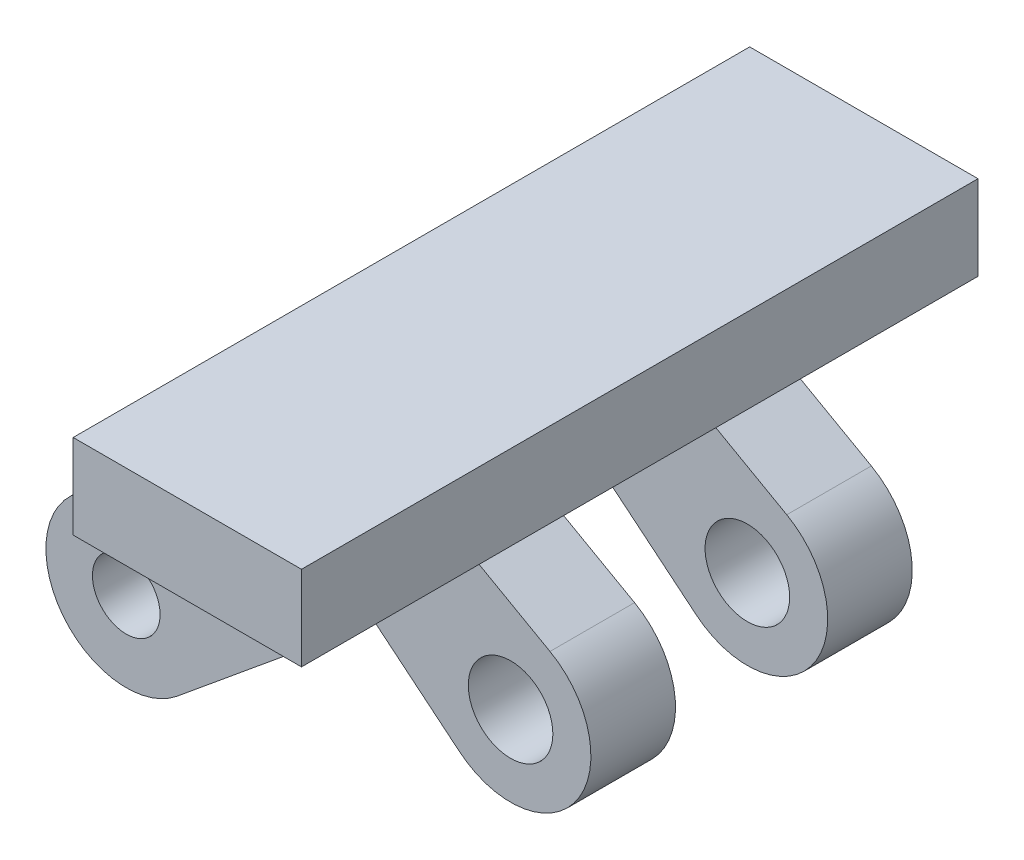
SolidWorks part; units mm, degrees
ref_plane "前视基准面" through (0, 0, 0) normal (0, 0, 1) x (1, 0, 0)
ref_plane "上视基准面" through (0, 0, 0) normal (0, 1, 0) x (1, 0, 0)
ref_plane "右视基准面" through (0, 0, 0) normal (1, 0, 0) x (0, 0, -1)
sketch "草图1" plane through (0, 0, 0) normal (0, 0, 1) x (1, 0, 0)
  line L1 (0, 0) -> (5.4, 0)
  line L2 (0, 0) -> (0, -2)
  line L3 (0, -2) -> (5.4, -2)
  line L4 (5.4, 0) -> (5.4, -2)
  dimension "D1" = 2
  dimension "D2" = 5.4
extrude "凸台-拉伸1" add sketch "草图1" along normal blind 8 and the other way blind 8
ref_plane "基准面2" through (0, 0, 6) normal (0, 0, 1) x (1, 0, 0)
sketch "草图3" plane through (0, 0, 6) normal (0, 0, 1) x (1, 0, 0)
  line L0 (0, -2) -> (-1.6772, -2.9444)
  line L1 (5.4, -2) -> (0.463, -6.0666)
  line L2 (0, -2) -> (5.4, -2) construction
  line L3 (0, -2) -> (5.4, -2)
  circle A0 centre (-0.745, -4.6) radius 1.9
  circle A1 centre (-0.745, -4.6) radius 0.8
  point P14 (2.7, -2)
  dimension "D1" = 1.6
  dimension "D2" = 3.8
  dimension "D3" = 2.6
  dimension "D4" = 3.445
extrude "凸台-拉伸2" add sketch "草图3" against normal blind 2 contours A0 A1 | A0 L1 L3 L0 region at (2.0907, -3.0871, 6) region at (0.1867, -3.0061, 6)
ref_plane "基准面1" through (0, 0, 3.8) normal (0, 0, 1) x (1, 0, 0)
sketch "草图5" plane through (0, 0, 3.8) normal (0, 0, 1) x (1, 0, 0)
  line L0 (5.4, -2) -> (7.0772, -2.9444)
  line L1 (0, -2) -> (4.937, -6.0666)
  line L2 (6.145, -4.6) -> (-0.745, -4.6) construction
  line L3 (0, -2) -> (5.4, -2)
  line L4 (0, -2) -> (5.4, -2) construction
  circle A0 centre (6.145, -4.6) radius 1.9
  circle A1 centre (6.145, -4.6) radius 1
  dimension "D1" = 3.8
  dimension "D2" = 2
  dimension "D3" = 6.89
extrude "凸台-拉伸3" add sketch "草图5" against normal blind 2 contours L2 A0 L0 L3 L1 | A1 A0 | A0 L2 L1 region at (3.2647, -2.9594, 3.8) region at (7.7389, -3.6683, 3.8) region at (3.9765, -4.9977, 3.8)
mirror "镜向1" about plane through (0, 0, 0) normal (0, 0, 1) of "凸台-拉伸2", "凸台-拉伸3"
